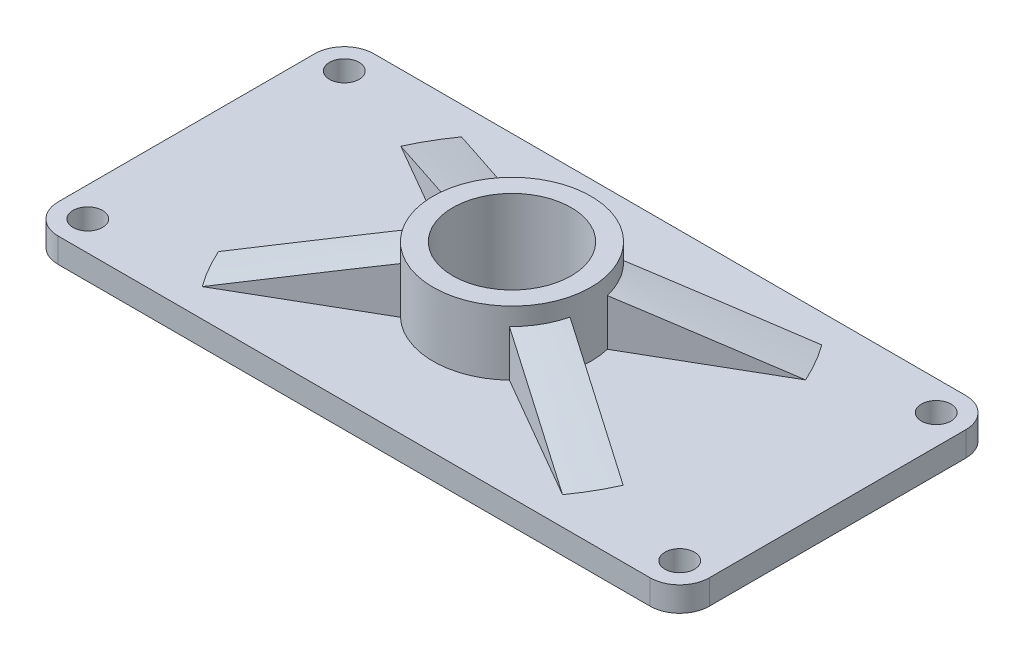
SolidWorks part; units mm, degrees
ref_plane "Front Plane" through (0, 0, 0) normal (0, 0, 1) x (1, 0, 0)
ref_plane "Top Plane" through (0, 0, 0) normal (0, 1, 0) x (1, 0, 0)
ref_plane "Right Plane" through (0, 0, 0) normal (1, 0, 0) x (0, 0, -1)
sketch "Sketch1" plane through (0, 0, 0) normal (0, 1, 0) x (1, 0, 0)
  line L0 (0, 0) -> (0, 49.8769) construction
  line L1 (0, 0) -> (-62.0874, 0) construction
  line L2 (-66, 26) -> (-66, -26)
  line L3 (-60, -32) -> (60, -32)
  line L4 (66, -26) -> (66, 26)
  line L5 (60, 32) -> (-60, 32)
  line L6 (-11.0471, -11.5742) -> (-36.7211, -26.3971)
  line L7 (-36.7211, -26.3971) -> (-41.2211, -18.6029)
  line L8 (-41.2211, -18.6029) -> (-15.5471, -3.78)
  line L9 (0, 0) -> (-112.3334, -64.8557) construction
  line L10 (-36.7211, 26.3971) -> (-41.2211, 18.6029)
  line L11 (-11.0471, 11.5742) -> (-36.7211, 26.3971)
  line L12 (-41.2211, 18.6029) -> (-15.5471, 3.78)
  line L13 (36.7211, -26.3971) -> (41.2211, -18.6029)
  line L14 (11.0471, -11.5742) -> (36.7211, -26.3971)
  line L15 (41.2211, -18.6029) -> (15.5471, -3.78)
  line L16 (41.2211, 18.6029) -> (15.5471, 3.78)
  line L17 (36.7211, 26.3971) -> (41.2211, 18.6029)
  line L18 (11.0471, 11.5742) -> (36.7211, 26.3971)
  circle A0 centre (0, 0) radius 12
  circle A1 centre (0, 0) radius 16
  arc A2 (-60, 32) -> (-66, 26) centre (-60, 26) ccw
  arc A3 (-60, -32) -> (-66, -26) centre (-60, -26) cw
  arc A4 (66, -26) -> (60, -32) centre (60, -26) cw
  arc A5 (66, 26) -> (60, 32) centre (60, 26) ccw
  circle A6 centre (-60, 26) radius 3
  circle A7 centre (-60, -26) radius 3
  circle A8 centre (60, 26) radius 3
  circle A9 centre (60, -26) radius 3
  point P20 (0, 32)
  point P21 (-66, 0)
  dimension "D1" = 24
  dimension "D2" = 32
  dimension "D3" = 6
  dimension "D4" = 6
  dimension "D5" = 6
  dimension "D6" = 6
  dimension "D9" = 45
  dimension "D7" = 132
  dimension "D8" = 64
  dimension "D10" = 9
  dimension "D12" = 30
extrude "Boss-Extrude1" add sketch "Sketch1" along normal blind 18 contours A1 A0 region at (-13.4645, 0, 7.7737)
extrude "Boss-Extrude2" add sketch "Sketch1<3>" along normal blind 5 contours L4 A5 L5 A2 L2 A3 L3 A4 A9 A8 A7 A6 A1 L15 L13 L14 L6 L7 L8 L12 L10 L11 L18 L17 L16 region at (-63.2053, 0, -29.2053)
sketch "Sketch1<3>" plane through (0, 0, 0) normal (0, 1, 0) x (1, 0, 0) same geometry as "Sketch1"
extrude "Boss-Extrude4" add sketch "Sketch1<6>" along normal blind 18 contours A1 L11 L10 L12 | A1 L16 L17 L18 | A1 L14 L13 L15 | A1 L8 L7 L6 region at (-26.3208, 0, 15.1963) region at (26.3208, 0, 15.1963) region at (-26.3208, 0, -15.1963) region at (26.3208, 0, -15.1963)
sketch "Sketch1<6>" plane through (0, 0, 0) normal (0, 1, 0) x (1, 0, 0) same geometry as "Sketch1"
ref_axis "Axis2" through (0, 18.9, 0) along (0, -1, 0)
ref_plane "Plane4" through (0, 0, 0) normal (-1, 0, 0) x (0, -1, 0)
sketch "Sketch18" plane through (0, 0, 0) normal (-1, 0, 0) x (0, -1, 0)
  line L0 (-14.4227, 16) -> (-5, 45)
  line L1 (-18, 16) -> (-18, 45)
  line L2 (-18, 45) -> (-5, 45)
  line L3 (-18, 16) -> (-14.4227, 16)
  line L4 (-5, 45) -> (-5, 49.2197) construction
  line L5 (-18.9, 0) -> (0.9, 0) construction
  line L6 (-5, 32) -> (-5, 50.2849) construction
  line L8 (-18, 45) -> (-18, 47.4988)
  line L9 (-18, 47.4988) -> (-5, 47.4988)
  line L10 (-5, 47.4988) -> (-5, 45)
  point P7 (-13.6044, 16)
  dimension "D1" = 162
  dimension "D2" = 45
  dimension "D3" = 16
  dimension "D4" = 13
  dimension "D5" = 18
revolve "Cut-Revolve4" cut sketch "Sketch18" angle 360 about axis through (0, 18.9, 0) along (0, -1, 0) region at (0, 13.4093, 33.2473) region at (0, 11.5, 46.2494)
